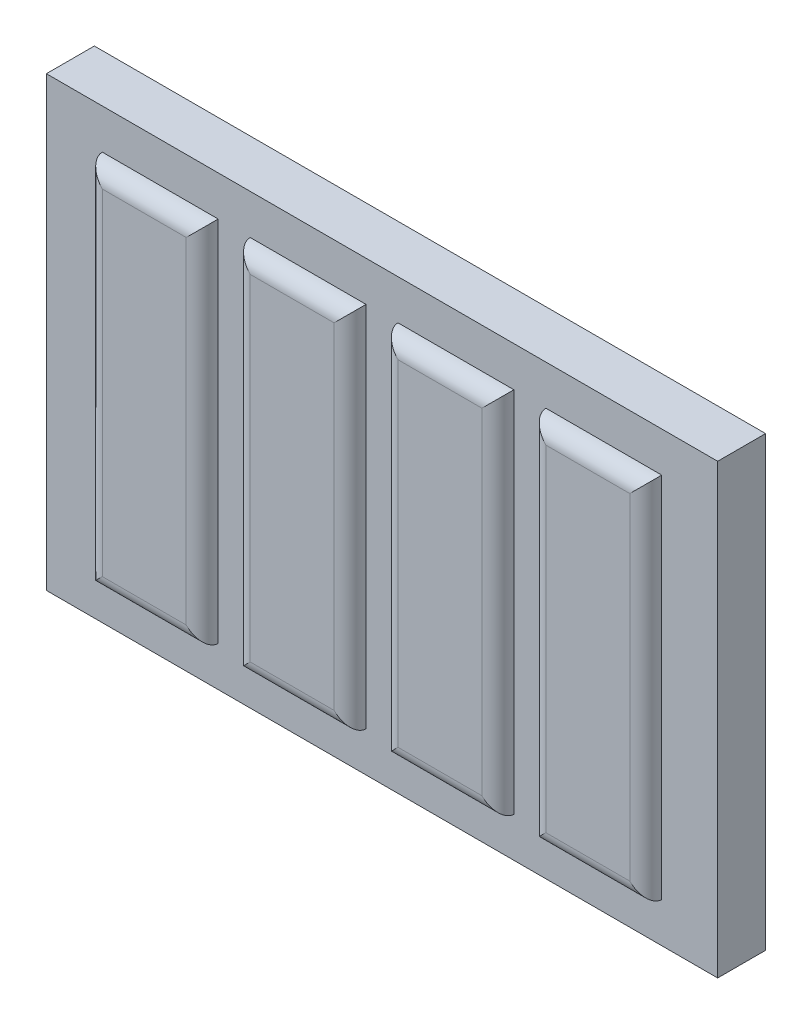
SolidWorks part; units mm, degrees
material "Plain Carbon Steel"
ref_plane "Front Plane" through (0, 0, 0) normal (0, 0, 1) x (1, 0, 0)
ref_plane "Top Plane" through (0, 0, 0) normal (0, 1, 0) x (1, 0, 0)
ref_plane "Right Plane" through (0, 0, 0) normal (1, 0, 0) x (0, 0, -1)
sketch "Sketch1" plane through (0, 0, 0) normal (0, 0, 1) x (1, 0, 0)
  line L0 (0, 0) -> (10.668, 0)
  line L1 (10.668, 0) -> (10.668, 7.112)
  line L2 (10.668, 7.112) -> (0, 7.112)
  line L3 (0, 7.112) -> (0, 0)
  dimension "D1" = 7.112
  dimension "D2" = 10.668
extrude "Boss-Extrude1" add sketch "Sketch1" along normal blind 0.762
sketch "Sketch2" plane through (0, 0, 0.762) normal (0, 0, 1) x (1, 0, 0)
  line L1 (9.779, 6.477) -> (9.779, 0.635)
  line L3 (0.889, 0.635) -> (0.889, 6.477)
  line L4 (2.7305, 6.477) -> (2.7305, 0.635)
  line L5 (3.2385, 6.477) -> (3.2385, 0.635)
  line L6 (5.08, 6.477) -> (5.08, 0.635)
  line L7 (5.588, 6.477) -> (5.588, 0.635)
  line L8 (7.4295, 6.477) -> (7.4295, 0.635)
  line L9 (7.9375, 6.477) -> (7.9375, 0.635)
  line L10 (0, 7.112) -> (0, 0) construction
  line L12 (0.889, 6.477) -> (2.7305, 6.477)
  line L13 (3.2385, 6.477) -> (5.08, 6.477)
  line L14 (5.588, 6.477) -> (7.4295, 6.477)
  line L15 (7.9375, 6.477) -> (9.779, 6.477)
  line L16 (0.889, 0.635) -> (2.7305, 0.635)
  line L17 (3.2385, 0.635) -> (5.08, 0.635)
  line L18 (5.588, 0.635) -> (7.4295, 0.635)
  line L19 (7.9375, 0.635) -> (9.779, 0.635)
  dimension "D1" = 8.89
  dimension "D2" = 0.889
  dimension "D3" = 5.842
  dimension "D4" = 5.842
  dimension "D5" = 0.508
  dimension "D6" = 1.8415
  dimension "D7" = 1.8415
  dimension "D8" = 1.8415
  dimension "D9" = 1.8415
  dimension "D10" = 0.508
  dimension "D11" = 0.508
extrude "Boss-Extrude2" add sketch "Sketch2" along normal blind 0.254
fillet "Fillet1" radius 0.254 16 edges at (2.7305, 3.556, 1.016) (1.8097, 0.635, 1.016) (0.889, 3.556, 1.016) (1.8097, 6.477, 1.016) (5.08, 3.556, 1.016) (4.1592, 0.635, 1.016) (3.2385, 3.556, 1.016) (4.1592, 6.477, 1.016) (9.779, 3.556, 1.016) (8.8582, 0.635, 1.016) (7.9375, 3.556, 1.016) (8.8582, 6.477, 1.016) (7.4295, 3.556, 1.016) (6.5087, 0.635, 1.016) (5.588, 3.556, 1.016) (6.5087, 6.477, 1.016)
